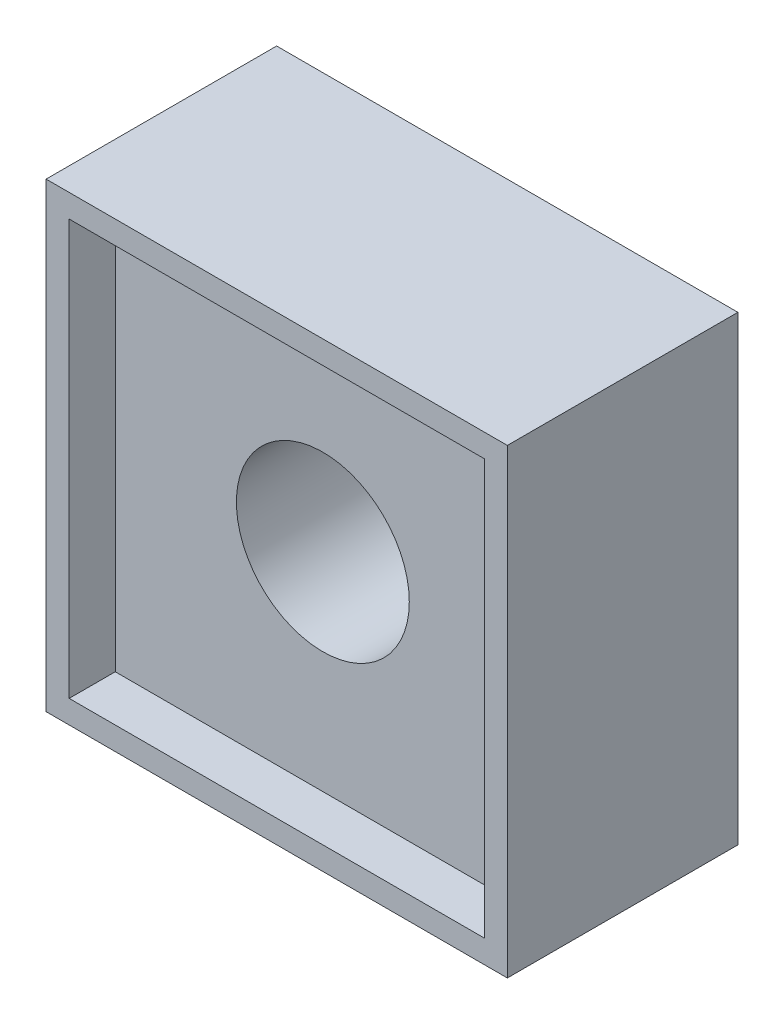
SolidWorks part; units mm, degrees
ref_plane "Front Plane" through (0, 0, 0) normal (0, 0, 1) x (1, 0, 0)
ref_plane "Top Plane" through (0, 0, 0) normal (0, 1, 0) x (1, 0, 0)
ref_plane "Right Plane" through (0, 0, 0) normal (1, 0, 0) x (0, 0, -1)
sketch "Sketch1" plane through (0, 0, 0) normal (0, 0, 1) x (1, 0, 0)
  line L1 (20.0076, -20.0076) -> (-20.0076, -20.0076)
  line L2 (20.0076, -20.0076) -> (20.0076, 20.0076)
  line L3 (20.0076, 20.0076) -> (-20.0076, 20.0076)
  line L4 (-20.0076, -20.0076) -> (-20.0076, 20.0076)
  line L5 (11.1, -18.5076) -> (-11.3, -18.5076)
  line L6 (11.1, -18.5076) -> (11.1, -14.2076)
  line L7 (11.1, -14.2076) -> (-11.3, -14.2076)
  line L8 (-11.3, -18.5076) -> (-11.3, -14.2076)
  line L9 (11.1, 14.4076) -> (-11.3, 14.4076)
  line L10 (11.1, 14.4076) -> (11.1, 18.7076)
  line L11 (11.1, 18.7076) -> (-11.3, 18.7076)
  line L12 (-11.3, 14.4076) -> (-11.3, 18.7076)
  circle A0 centre (0, 0) radius 9.25
  circle A1 centre (0, 0) radius 7.5
  circle A2 centre (0, 0) radius 8.95
  dimension "D6" = 15
  dimension "D7" = 17.9
  dimension "D2" = 4.3
  dimension "D3" = 4.3
  dimension "D4" = 22.4
  dimension "D5" = 22.4
  dimension "D1" = 0.3
extrude "Boss-Extrude1" add sketch "Sketch1" along normal blind 20 contours L1 L4 L3 L2
extrude "Boss-Extrude2" add sketch "Sketch1<3>" against normal blind 3.5 contours A2 A1 region at (-8.6969, 0, 0)
sketch "Sketch1<3>" plane through (0, 0, 0) normal (0, 0, 1) x (1, 0, 0) same geometry as "Sketch1"
extrude "Cut-Extrude1" cut sketch "Sketch1<4>" along normal through all contours A1 region at (0, 0, 0)
sketch "Sketch1<4>" plane through (0, 0, 0) normal (0, 0, 1) x (1, 0, 0) same geometry as "Sketch1"
extrude "Cut-Extrude2" cut sketch "Sketch1<5>" along normal blind 6.7 contours L8 L5 L6 L7 | L12 L9 L10 L11 region at (-0.1, -16.3576, 0) region at (-0.1, 16.5576, 0)
sketch "Sketch1<5>" plane through (0, 0, 0) normal (0, 0, 1) x (1, 0, 0) same geometry as "Sketch1"
sketch "Sketch7" plane through (0, 0, 20) normal (0, 0, 1) x (1, 0, 0)
  line L14 (-18.0076, 18.0076) -> (-18.0076, -18.0076)
  line L15 (18.0076, 18.0076) -> (-18.0076, 18.0076)
  line L16 (18.0076, -18.0076) -> (18.0076, 18.0076)
  line L17 (-18.0076, -18.0076) -> (18.0076, -18.0076)
  line L18 (-18.0076, 18.0076) -> (-18.0076, -18.0076)
  line L19 (18.0076, 18.0076) -> (-18.0076, 18.0076)
  line L20 (18.0076, -18.0076) -> (18.0076, 18.0076)
  line L21 (-18.0076, -18.0076) -> (18.0076, -18.0076)
  dimension "D1" = 2
extrude "Cut-Extrude3" cut sketch "Sketch7" against normal blind 4
